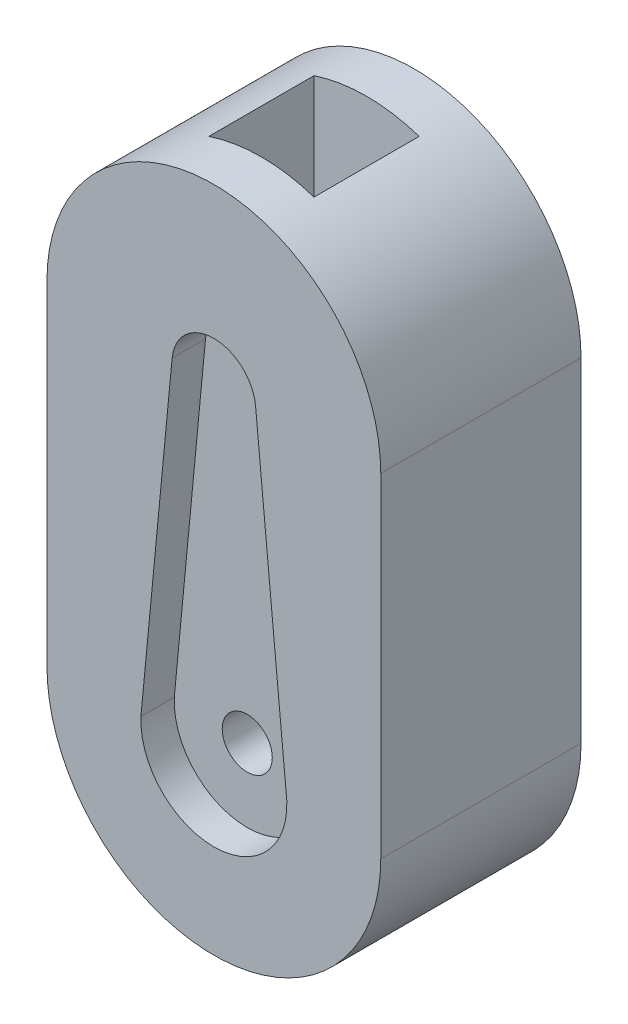
SolidWorks part; units mm, degrees
material "ABS"
ref_plane "Front Plane" through (0, 0, 0) normal (0, 0, 1) x (1, 0, 0)
ref_plane "Top Plane" through (0, 0, 0) normal (0, 1, 0) x (1, 0, 0)
ref_plane "Right Plane" through (0, 0, 0) normal (1, 0, 0) x (0, 0, -1)
sketch "Sketch1" plane through (0, 0, 0) normal (0, 0, 1) x (1, 0, 0)
  line L0 (0, 20) -> (0, 0) construction
  line L1 (10, 20) -> (10, 0)
  line L2 (-10, 20) -> (-10, 0)
  arc A1 (10, 20) -> (-10, 20) centre (0, 20) ccw
  arc A2 (-10, 0) -> (10, 0) centre (0, 0) ccw
  point P3 (0, 10)
  point P9 (0, 30)
  point P10 (0, -10)
  dimension "D1" = 20
  dimension "D2" = 40
sketch "Sketch2" plane through (0, 0, 0) normal (0, 0, 1) x (1, 0, 0)
  line L0 (0, 0) -> (0, 30) construction
  line L1 (-2.5, 19.7394) -> (-4.37, 0.2091)
  line L2 (2.5, 19.7394) -> (4.37, 0.2091)
  line L3 (-10, 0) -> (10, 0) construction
  line L8 (-10, 20) -> (-10, 0) construction
  line L9 (10, 20) -> (10, 0) construction
  arc A0 (-4.37, 0.2091) -> (4.37, -0.2091) centre (0, 0) ccw
  arc A2 (-2.5, 19.7394) -> (2.5, 19.7394) centre (0, 19.5) cw
  arc A3 (4.37, -0.2091) -> (4.37, 0.2091) centre (0, 0) ccw
  arc A5 (10, 20) -> (-10, 20) centre (0, 20) ccw construction
  dimension "D1" = 4.375
  dimension "D2" = 8.74
  dimension "D3" = 19.5
  dimension "D4" = 5
extrude "Boss-Extrude1" add sketch "Sketch1" against normal blind 12
sketch "Sketch4" plane through (0, 0, 0) normal (0, 0, 1) x (1, 0, 0)
  circle A0 centre (0, 0) radius 1.5
  dimension "D1" = 3
extrude "Cut-Extrude2" cut sketch "Sketch4" against normal through all
extrude "Cut-Extrude1" cut sketch "Sketch2" against normal blind 2
ref_plane "Plane1" through (0, 5, 0) normal (0, 1, 0) x (1, 0, 0)
sketch "Sketch6" plane through (0, 5, 0) normal (0, -1, 0) x (-1, 0, 0)
  line L0 (0, 12) -> (0, 0) construction
  line L13 (10, 12) -> (-10, 12) construction
  line L15 (-3.15, 9.15) -> (3.15, 9.15)
  line L17 (-3.15, 9.15) -> (-3.15, 2.85)
  line L18 (-3.15, 2.85) -> (3.15, 2.85)
  line L21 (3.15, 9.15) -> (3.15, 2.85)
  line L22 (-3.15, 9.15) -> (3.15, 2.85) construction
  line L23 (-3.15, 2.85) -> (3.15, 9.15) construction
  point P4 (0, 6)
  dimension "D1" = 6.3
extrude "Cut-Extrude3" cut sketch "Sketch6" against normal through all
ref_axis "Axis1" through (0, 0, -12) along (0, 0, 1)
ref_plane "Plane2" through (0, 0, -6) normal (0, 0, 1) x (1, 0, 0)
mirror "Mirror1" about plane through (0, 0, -6) normal (0, 0, 1) of "Cut-Extrude1"
